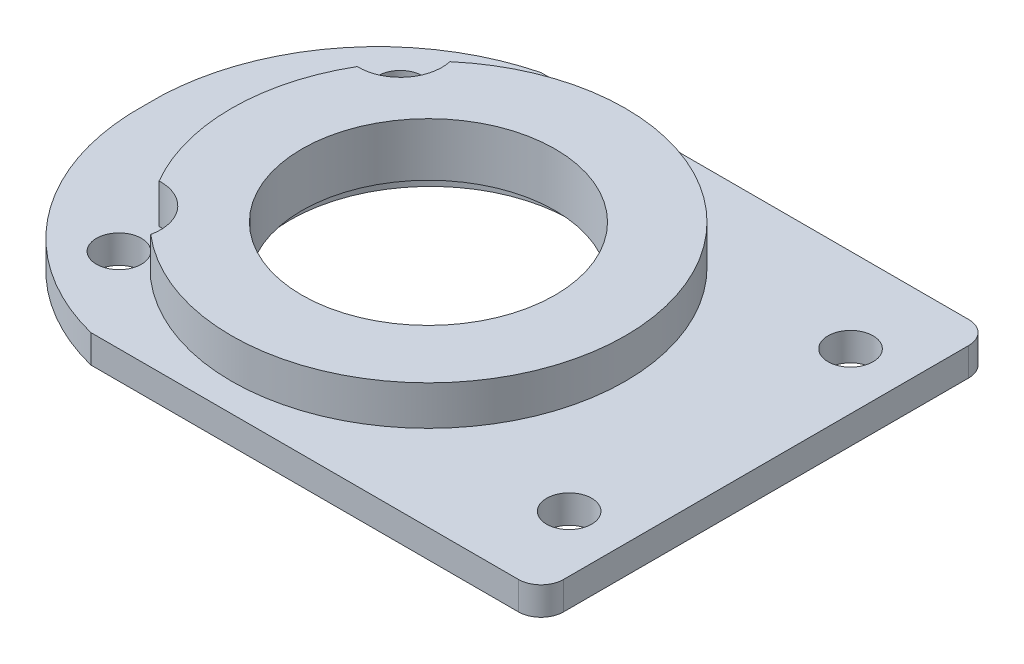
SolidWorks part; units mm, degrees
ref_plane "Front Plane" through (0, 0, 0) normal (0, 0, 1) x (1, 0, 0)
ref_plane "Top Plane" through (0, 0, 0) normal (0, 1, 0) x (1, 0, 0)
ref_plane "Right Plane" through (0, 0, 0) normal (1, 0, 0) x (0, 0, -1)
sketch "Sketch1" plane through (0, 0, 0) normal (0, 1, 0) x (1, 0, 0)
  line L1 (0, 0) -> (76.2, 0)
  line L2 (0, 0) -> (0, 50.8)
  line L3 (0, 50.8) -> (76.2, 50.8)
  line L4 (76.2, 0) -> (76.2, 50.8)
  circle A0 centre (38.1, 25.4) radius 14.2748
  dimension "D5" = 28.5496
  dimension "D1" = 50.8
  dimension "D2" = 76.2
  dimension "D3" = 38.1
  dimension "D4" = 25.4
extrude "Boss-Extrude1" add sketch "Sketch1" along normal blind 3.175
sketch "Sketch2" plane through (0, 3.175, 0) normal (0, 1, 0) x (1, 0, 0)
  circle A0 centre (38.1, 25.4) radius 22.225
  dimension "D1" = 44.45
extrude "Boss-Extrude2" add sketch "Sketch2" along normal blind 4.445
sketch "Sketch3" plane through (0, 3.175, 0) normal (0, -1, 0) x (1, 0, 0)
  circle A0 centre (38.1, -25.4) radius 14.2875
  dimension "D1" = 28.575
sketch "Sketch4" plane through (0, 0, 0) normal (0, -1, 0) x (-1, 0, 0)
  line L0 (0, 0) -> (-76.2, 0) construction
  circle A0 centre (-38.3325, 25.4) radius 15.8623
  dimension "D1" = 31.7246
  dimension "D2" = 25.4
extrude "Cut-Extrude2" cut sketch "Sketch4" against normal blind 1.6002
fillet "Fillet2" radius 2.54 4 edges at (0, 1.5875, -50.8) (76.2, 1.5875, -50.8) (0, 1.5875, 0) (76.2, 1.5875, 0)
sketch "Sketch5" plane through (0, 3.175, 0) normal (0, 1, 0) x (1, 0, 0)
  line L0 (73.66, 50.8) -> (2.54, 50.8) construction
  line L2 (2.54, 0) -> (73.66, 0) construction
  line L3 (76.2, 2.54) -> (76.2, 48.26) construction
  circle A0 centre (69.85, 41.275) radius 2.54
  circle A1 centre (69.85, 9.525) radius 2.54
  circle A2 centre (19.05, 9.525) radius 2.54
  circle A3 centre (19.05, 41.275) radius 2.54
  dimension "D9" = 5.08
  dimension "D10" = 5.08
  dimension "D11" = 5.08
  dimension "D12" = 5.08
  dimension "D1" = 9.525
  dimension "D2" = 50.8
  dimension "D3" = 50.8
  dimension "D4" = 9.525
  dimension "D5" = 9.525
  dimension "D6" = 6.35
  dimension "D7" = 9.525
  dimension "D8" = 6.35
extrude "Cut-Extrude3" cut sketch "Sketch5" against normal through all and the other way through all
sketch "Sketch6" plane through (0, 3.175, 0) normal (0, 1, 0) x (1, 0, 0)
  line L0 (2.54, 0) -> (73.66, 0) construction
  line L1 (0, 0) -> (0, 50.8)
  line L2 (73.66, 50.8) -> (2.54, 50.8) construction
  line L3 (25.4, 0) -> (0, 0)
  line L5 (25.4, 50.8) -> (0, 50.8)
  arc A0 (25.4, 0) -> (6.234, 25.3597) centre (31.6234, 24.6258) cw
  arc A1 (25.4, 50.8) -> (6.234, 25.3597) centre (31.6209, 26.1736) ccw
  line M6 (73.66, 50.8) -> (2.54, 50.8)
  arc M7 (2.54, 50.8) -> (0, 48.26) centre (2.54, 48.26) ccw
  line M8 (0, 48.26) -> (0, 2.54)
  arc M9 (0, 2.54) -> (2.54, 0) centre (2.54, 2.54) ccw
  line M10 (2.54, 0) -> (73.66, 0)
extrude "Cut-Extrude4" cut sketch "Sketch6" along direction (0, -1, 0) on the side against the normal through all contours A1 A0 M6 M7 M8 M9 M10 region at (0.568, 3.175, -25.4)
sketch "Sketch7" plane through (0, 3.175, 0) normal (0, 1, 0) x (1, 0, 0)
  circle A0 centre (19.05, 9.525) radius 4.699
  dimension "D1" = 9.398
extrude "Cut-Extrude5" cut sketch "Sketch7" along normal through all contours A0
sketch "Sketch9" plane through (0, 3.175, 0) normal (0, 1, 0) x (1, 0, 0)
  circle A0 centre (19.05, 41.275) radius 4.699
  dimension "D1" = 9.398
extrude "Cut-Extrude6" cut sketch "Sketch9" along normal through all contours A0
extrude "Cut-Extrude8" cut sketch "Sketch3" against normal through all and the other way through all contours A0
